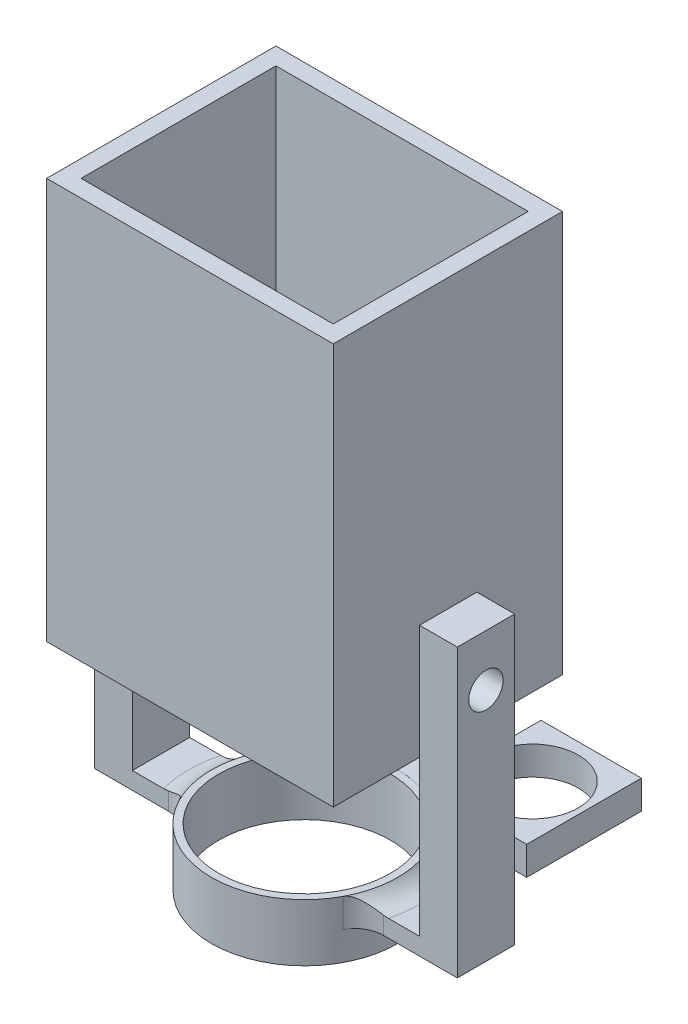
SolidWorks part; units mm, degrees
ref_plane "Front Plane" through (0, 0, 0) normal (0, 0, 1) x (1, 0, 0)
ref_plane "Top Plane" through (0, 0, 0) normal (0, 1, 0) x (1, 0, 0)
ref_plane "Right Plane" through (0, 0, 0) normal (1, 0, 0) x (0, 0, -1)
sketch "Sketch2" plane through (0, 0, 0) normal (0, 1, 0) x (1, 0, 0)
  line L0 (0, 15) -> (0, -15) construction
  line L1 (-15, 0) -> (15, 0) construction
  line L2 (-15, 0) -> (-15, 5) construction
  line L3 (-14.1421, 5) -> (-31.6421, 5)
  line L4 (-31.6421, 5) -> (-31.6421, -5)
  line L5 (-14.1421, -5) -> (-31.6421, -5)
  line L6 (14.1421, -5) -> (31.6421, -5)
  line L7 (31.6421, 5) -> (31.6421, -5)
  line L8 (14.1421, 5) -> (31.6421, 5)
  line L9 (0, 16.25) -> (22.5, 16.25)
  line L10 (22.5, 16.25) -> (22.5, 36.25)
  line L11 (22.5, 36.25) -> (5, 36.25)
  line L12 (-22.5, 36.25) -> (-22.5, 16.25)
  line L13 (-22.5, 16.25) -> (0, 16.25)
  line L14 (22.5, 26.25) -> (21.5, 26.25) construction
  line L20 (-5, 36.25) -> (-22.5, 36.25)
  line L21 (0, 31.25) -> (0, 16.25) construction
  line L22 (-5, 36.25) -> (-5, 31.25)
  line L23 (-5, 31.25) -> (5, 31.25)
  line L24 (5, 31.25) -> (5, 36.25)
  line L25 (13.5, 34.25) -> (13.5, 36.25) construction
  line L26 (13.5, 18.25) -> (13.5, 16.25) construction
  line L27 (-13.5, 26.25) -> (13.5, 26.25) construction
  line L28 (-13.5, 9.045) -> (-13.5, 16.25)
  line L29 (13.5, 16.25) -> (13.5, 9.045)
  line L30 (-16.25, 0) -> (-25.05, 0) construction
  line L31 (-25.05, 5) -> (-25.05, -5)
  line L32 (25.05, 5) -> (25.05, -5)
  circle A0 centre (0, 0) radius 15
  circle A1 centre (0, 0) radius 16.25
  circle A2 centre (13.5, 26.25) radius 8
  circle A3 centre (-13.5, 26.25) radius 8
  point P13 (-31.6421, 0)
  dimension "D1" = 30
  dimension "D2" = 17.5
  dimension "D4" = 32.5
  dimension "D8" = 1
  dimension "D9" = 16
  dimension "D3" = 5
  dimension "D5" = 5
  dimension "D6" = 20
  dimension "D7" = 45
  dimension "D10" = 17.5
  dimension "D11" = 8.8
extrude "Connector sleeve" add sketch "Sketch2" along normal blind 5 and the other way blind 5 contours L5 A1 L6 A0 | L8 A1 L3 A0 | L6 A1 L8 A0 | L3 A1 L5 A0 region at (-14.3253, 0, -6.9471) region at (-15.3497, 0, 0) region at (-14.8019, 0, 5.3291) region at (15.3497, 0, 0)
ref_plane "Plane2" through (0, 30, 0) normal (0, 1, 0) x (1, 0, 0)
sketch "Sketch3" plane through (0, 30, 0) normal (0, 1, 0) x (1, 0, 0)
  line L1 (-25, 20) -> (25, 20)
  line L2 (-25, 20) -> (-25, -20)
  line L3 (-25, -20) -> (25, -20)
  line L4 (25, 20) -> (25, -20)
  line L5 (-25, 20) -> (25, -20) construction
  line L6 (-25, -20) -> (25, 20) construction
  circle A0 centre (0, 0) radius 3
  point P0 (0, 0)
  dimension "D3" = 6
  dimension "D1" = 50
  dimension "D2" = 40
extrude "Motor casing" add sketch "Sketch3" along normal blind 70
shell "Shell4" thickness 3 removed face at (0, 100, 3) removed face at (0, 100, 0)
sketch "Sketch6" plane through (0, 33, 0) normal (0, 1, 0) x (1, 0, 0)
  circle A0 centre (0, 0) radius 15
  circle A1 centre (0, 0) radius 16
  dimension "D1" = 30
  dimension "D2" = 32
extrude "Motor sits here" add sketch "Sketch6" along normal blind 30
extrude "Sleeve-casing connector" add sketch "Sketch2<16>" along normal blind 3 contours A1 L3 L31 L5 | L31 L3 L4 L5 | A1 L6 L32 L8 | L8 L32 L6 L7 region at (-28.3461, 0, 0) region at (-20.5169, 0, 0) region at (20.5169, 0, 0) region at (28.3461, 0, 0)
sketch "Sketch2<16>" plane through (0, 0, 0) normal (0, 1, 0) x (1, 0, 0) same geometry as "Sketch2"
extrude "Sleeve-casing arms" add sketch "Sketch2<17>" along normal blind 50 contours L31 L3 L4 L5 | L8 L32 L6 L7 region at (-28.3461, 0, 0) region at (28.3461, 0, 0)
sketch "Sketch2<17>" plane through (0, 0, 0) normal (0, 1, 0) x (1, 0, 0) same geometry as "Sketch2"
extrude "Sensor holder" add sketch "Sketch2<10>" along normal blind 5 separate body contours L24 L23 L22 L20 L12 L13 L9 L10 L11 A2 A3 | A1 L13 L28 | A1 L29 L9 region at (-10.2927, 0, -14.2057) region at (0, 0, -25.4127) region at (10.2927, 0, -14.2057)
sketch "Sketch2<10>" plane through (0, 0, 0) normal (0, 1, 0) x (1, 0, 0) same geometry as "Sketch2"
fillet "Fillet2" radius 5 6 edges at (-15.4616, 1.5, -5) (-16.25, 3, 0) (-15.4616, 1.5, 5) (15.4616, 1.5, 5) (15.4616, 1.5, -5) (16.25, 3, 0)
ref_plane "Plane4" through (-31.6421, 0, 0) normal (-1, 0, 0) x (0, 0, 1)
sketch "Sketch8" plane through (-31.6421, 0, 0) normal (-1, 0, 0) x (0, 0, 1)
  line L0 (0, 50) -> (0, 41) construction
  line L1 (-5, 50) -> (5, 50) construction
  circle A0 centre (0, 41) radius 3
  dimension "D2" = 3
  dimension "D1" = 9
extrude "Cut-Extrude5" cut sketch "Sketch8" against normal through all both and the other way through all
